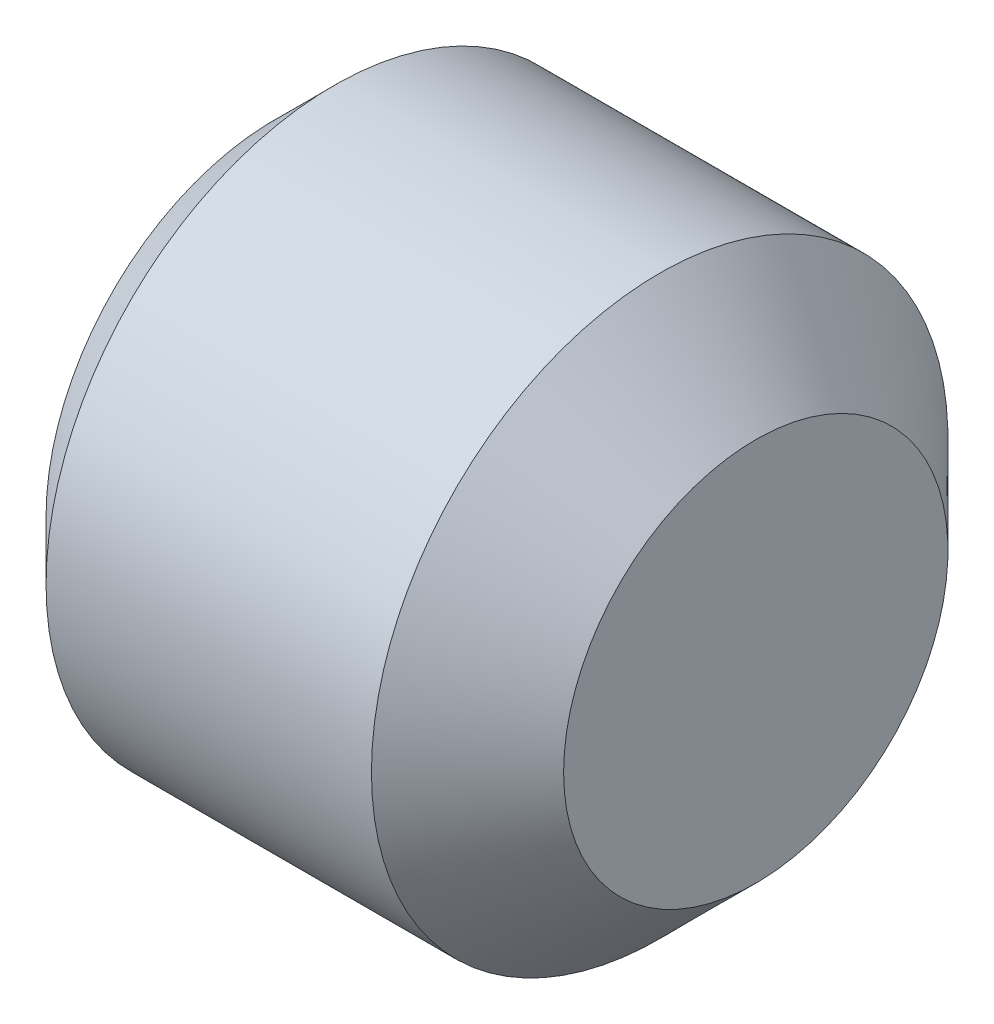
SolidWorks part; units mm, degrees
material "A6061"
ref_plane "前视基准面" through (0, 0, 0) normal (0, 0, 1) x (1, 0, 0)
ref_plane "上视基准面" through (0, 0, 0) normal (0, 1, 0) x (1, 0, 0)
ref_plane "右视基准面" through (0, 0, 0) normal (1, 0, 0) x (0, 0, -1)
sketch "草图1" plane through (0, 0, 0) normal (0, 0, 1) x (1, 0, 0)
  line L0 (-5, 0) -> (-5, 2.3865)
  line L1 (-5, 2.3865) -> (-4.3865, 3)
  line L2 (-4.3865, 3) -> (-1, 3)
  line L3 (-1, 3) -> (0, 2)
  line L4 (0, 2) -> (0, 0)
  line L5 (0, 0) -> (-5, 0)
  line L6 (0, 0) -> (-5, 0) construction
revolve "旋转1" add sketch "草图1" angle 360 about L6 reverse direction yes
cosmetic thread "装饰螺纹线1" parameters "D1"=5, "D2"=4.773
ref_plane "基准面1" through (-5, 0, 0) normal (-1, 0, 0) x (0, 0, 1)
sketch "草图2" plane through (-5, 0, 0) normal (-1, 0, 0) x (0, 0, 1)
  line L0 (0.866, -1.5) -> (1.7321, 0)
  line L1 (1.7321, 0) -> (0.866, 1.5)
  line L2 (0.866, 1.5) -> (-0.866, 1.5)
  line L3 (-0.866, 1.5) -> (-1.7321, 0)
  line L4 (-1.7321, 0) -> (-0.866, -1.5)
  line L5 (-0.866, -1.5) -> (0.866, -1.5)
extrude "切除-拉伸1" cut sketch "草图2" against normal blind 2
sketch "草图3" plane through (0, 0, 0) normal (0, 0, 1) x (1, 0, 0)
  line L0 (-3, 0) -> (-3, 1.5)
  line L1 (-3, 1.5) -> (-2.134, 0)
  line L2 (-2.134, 0) -> (-3, 0)
  line L3 (-2.134, 0) -> (-3, 0) construction
revolve "切除-旋转1" cut sketch "草图3" angle 360 about L3 reverse direction yes
ref_plane "CP XY" through (0, 0, 0) normal (1, 0, 0) x (0, 0, -1)
ref_plane "CP XZ" through (0, 0, 0) normal (0, -1, 0) x (-1, 0, 0)
ref_plane "CP YZ" through (0, 0, 0) normal (0, 0, -1) x (-1, 0, 0)
ref_axis "CP X" through (0, 0, 80.9) along (0, 0, -1)
ref_axis "CP Y" through (0, -50, 0) along (0, 1, 0)
ref_axis "CP Z" through (80.9, 0, 0) along (-1, 0, 0)
sketch3d "CP"
  point P0 (0, 0, 0)
